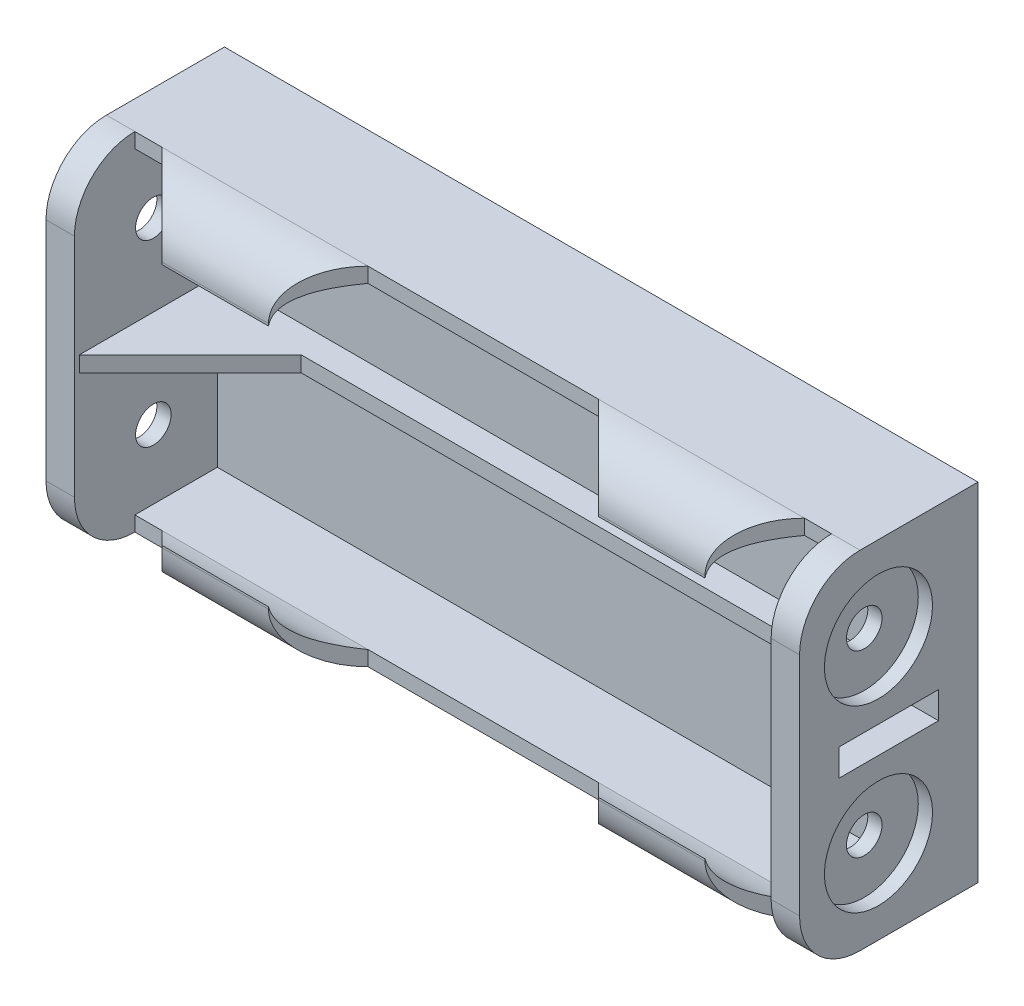
SolidWorks part; units mm, degrees
ref_plane "Přední rovina" through (0, 0, 0) normal (0, 0, 1) x (1, 0, 0)
ref_plane "Horní rovina" through (0, 0, 0) normal (0, 1, 0) x (1, 0, 0)
ref_plane "Pravá rovina" through (0, 0, 0) normal (1, 0, 0) x (0, 0, -1)
sketch "Skica1" plane through (0, 0, 0) normal (0, 0, 1) x (1, 0, 0)
  line L1 (-26.5, -12.2) -> (26.5, -12.2)
  line L2 (-26.5, -12.2) -> (-26.5, 12.2)
  line L3 (-26.5, 12.2) -> (26.5, 12.2)
  line L4 (26.5, -12.2) -> (26.5, 12.2)
  line L5 (-26.5, -12.2) -> (26.5, 12.2) construction
  line L6 (-26.5, 12.2) -> (26.5, -12.2) construction
  point P0 (0, 0)
  dimension "D1" = 53
  dimension "D2" = 24.4
extrude "Přidat vysunutím1" add sketch "Skica1" along normal blind 2.5
sketch "Skica2" plane through (0, 0, 2.5) normal (0, 0, 1) x (1, 0, 0)
  line L0 (26.5, 12.2) -> (-26.5, 12.2) construction
  line L1 (-24.5, 11.15) -> (24.5, 11.15)
  line L2 (-24.5, 11.15) -> (-24.5, 12.2)
  line L3 (-24.5, 12.2) -> (24.5, 12.2)
  line L4 (24.5, 11.15) -> (24.5, 12.2)
  line L5 (-26.5, 12.2) -> (-26.5, -12.2) construction
  line L6 (26.5, -12.2) -> (26.5, 12.2) construction
  line L7 (-26.5, -12.2) -> (26.5, -12.2) construction
  line L8 (-24.5, -12.2) -> (24.5, -12.2)
  line L9 (-24.5, -12.2) -> (-24.5, -11.15)
  line L10 (-24.5, -11.15) -> (24.5, -11.15)
  line L11 (24.5, -12.2) -> (24.5, -11.15)
  dimension "D1" = 2
  dimension "D2" = 2
  dimension "D3" = 2
  dimension "D4" = 2
  dimension "D5" = 1.05
  dimension "D6" = 1.05
extrude "Přidat vysunutím2" add sketch "Skica2" along normal blind 9.3
sketch "Skica3" plane through (0, 0, 11.8) normal (0, 0, 1) x (1, 0, 0)
  line L0 (-24.5, -12.2) -> (24.5, -12.2) construction
  line L1 (-8.1, -12.2) -> (8.1, -12.2)
  line L2 (-8.1, -12.2) -> (-8.1, -11.15)
  line L3 (-8.1, -11.15) -> (8.1, -11.15)
  line L4 (8.1, -12.2) -> (8.1, -11.15)
  line L5 (24.5, -11.15) -> (-24.5, -11.15) construction
  line L6 (24.5, 12.2) -> (-24.5, 12.2) construction
  line L7 (8.1, 12.2) -> (-8.1, 12.2)
  line L8 (8.1, 12.2) -> (8.1, 11.15)
  line L9 (8.1, 11.15) -> (-8.1, 11.15)
  line L10 (-8.1, 12.2) -> (-8.1, 11.15)
  line L11 (-24.5, 11.15) -> (24.5, 11.15) construction
  line L12 (0, 12.25) -> (0, -12.2) construction
  line L14 (-24.5, 11.15) -> (-22.6, 11.15)
  line L15 (-24.5, 11.15) -> (-24.5, 12.2)
  line L16 (-24.5, 12.2) -> (-22.6, 12.2)
  line L17 (-22.6, 11.15) -> (-22.6, 12.2)
  line L18 (-24.5, -12.2) -> (-22.6, -12.2)
  line L19 (-24.5, -12.2) -> (-24.5, -11.15)
  line L20 (-24.5, -11.15) -> (-22.6, -11.15)
  line L21 (-22.6, -12.2) -> (-22.6, -11.15)
  line L22 (24.5, 11.15) -> (22.6, 11.15)
  line L23 (24.5, 11.15) -> (24.5, 12.2)
  line L24 (24.5, 12.2) -> (22.6, 12.2)
  line L25 (22.6, 11.15) -> (22.6, 12.2)
  line L26 (24.5, -12.2) -> (22.6, -12.2)
  line L27 (24.5, -12.2) -> (24.5, -11.15)
  line L28 (24.5, -11.15) -> (22.6, -11.15)
  line L29 (22.6, -12.2) -> (22.6, -11.15)
  dimension "D1" = 16.2
  dimension "D2" = 1.9
  dimension "D3" = 1.9
extrude "Odebrat vysunutím1" cut sketch "Skica3" against normal blind 3.5
sketch "Skica6" plane through (0, -11.15, 0) normal (0, 1, 0) x (1, 0, 0)
  line L1 (22.6, -8.3) -> (8.1, -8.3)
  line L2 (22.6, -8.3) -> (22.6, -11.8)
  line L3 (22.6, -11.8) -> (8.1, -11.8)
  line L4 (8.1, -8.3) -> (8.1, -11.8)
  line L5 (-8.1, -8.3) -> (-22.6, -8.3)
  line L6 (-8.1, -8.3) -> (-8.1, -11.8)
  line L7 (-8.1, -11.8) -> (-22.6, -11.8)
  line L8 (-22.6, -8.3) -> (-22.6, -11.8)
sketch "Skica7" plane through (0, 11.15, 0) normal (0, -1, 0) x (-1, 0, 0)
  line L1 (22.6, -8.3) -> (8.1, -8.3)
  line L2 (22.6, -8.3) -> (22.6, -11.8)
  line L3 (22.6, -11.8) -> (8.1, -11.8)
  line L4 (8.1, -8.3) -> (8.1, -11.8)
  line L5 (-8.1, -8.3) -> (-22.6, -8.3)
  line L6 (-8.1, -8.3) -> (-8.1, -11.8)
  line L7 (-8.1, -11.8) -> (-22.6, -11.8)
  line L8 (-22.6, -8.3) -> (-22.6, -11.8)
extrude "Přidat vysunutím3" add sketch "Skica7" along normal blind 2.6
extrude "Přidat vysunutím4" add sketch "Skica6" along normal blind 2.6 contours L7 L8 L5 L6
sketch "Skica8" plane through (0, -11.15, 0) normal (0, 1, 0) x (1, 0, 0)
  line L1 (22.6, -8.3) -> (8.1, -8.3)
  line L2 (22.6, -8.3) -> (22.6, -11.8)
  line L3 (22.6, -11.8) -> (8.1, -11.8)
  line L4 (8.1, -8.3) -> (8.1, -11.8)
extrude "Přidat vysunutím5" add sketch "Skica8" along normal blind 2.6
fillet "Zaoblit3" radius 3.5 4 edges at (15.35, 12.2, 11.8) (-15.35, 12.2, 11.8) (-15.35, -12.2, 11.8) (15.35, -12.2, 11.8)
sketch "Skica11" plane through (22.6, 0, 0) normal (1, 0, 0) x (0, 0, -1)
  line L0 (-11.8, -8.55) -> (-8.3, -8.55)
  line L1 (-8.3, -8.55) -> (-8.3, -11.15)
  spline S0 degree 2 poles (-8.3, -11.15) (-11.4896, -10.5739) (-11.8, -8.55) knots 0 0 0 0.822636 0.822636 0.822636
extrude "Odebrat vysunutím2" cut sketch "Skica11" against normal up to vertex
sketch "Skica13" plane through (22.6, 0, 0) normal (1, 0, 0) x (0, 0, -1)
  line L0 (-11.8, 8.55) -> (-8.3, 8.55)
  line L1 (-8.3, 8.55) -> (-8.3, 11.15)
  spline S0 degree 2 poles (-8.3, 11.15) (-11.5945, 10.6267) (-11.8, 8.55) knots 0 0 0 0.882557 0.882557 0.882557
extrude "Odebrat vysunutím3" cut sketch "Skica13" against normal up to vertex
chamfer "Zkosení3" distance 3.5 angle 45 8 edges at (-22.6, -8.625, 11.8) (-22.6, 8.625, 11.8) (22.6, 8.625, 11.8) (22.6, -8.625, 11.8)
sketch "Skica14" plane through (0, 0, 2.5) normal (0, 0, 1) x (1, 0, 0)
  line L1 (26.5, -12.2) -> (24.5, -12.2)
  line L2 (26.5, -12.2) -> (26.5, 12.2)
  line L3 (26.5, 12.2) -> (24.5, 12.2)
  line L4 (24.5, -12.2) -> (24.5, 12.2)
  line L5 (-26.5, -12.2) -> (-24.5, -12.2)
  line L6 (-26.5, -12.2) -> (-26.5, 12.2)
  line L7 (-26.5, 12.2) -> (-24.5, 12.2)
  line L8 (-24.5, -12.2) -> (-24.5, 12.2)
extrude "Přidat vysunutím6" add sketch "Skica14" along normal blind 10.05
fillet "Zaoblit4" radius 4.25 4 edges at (-25.5, 12.2, 12.55) (-25.5, -12.2, 12.55) (25.5, -12.2, 12.55) (25.5, 12.2, 12.55)
sketch "Skica17" plane through (26.5, 0, 0) normal (1, 0, 0) x (0, 0, -1)
  line L0 (-12.55, 0) -> (0, 0) construction
  line L1 (-12.55, -7.95) -> (-12.55, 7.95) construction
  line L2 (0, -12.2) -> (0, 12.2) construction
  line L4 (-2.775, -0.95) -> (-9.775, -0.95)
  line L5 (-2.775, -0.95) -> (-2.775, 0.95)
  line L6 (-2.775, 0.95) -> (-9.775, 0.95)
  line L7 (-9.775, -0.95) -> (-9.775, 0.95)
  line L8 (-2.775, -0.95) -> (-9.775, 0.95) construction
  line L9 (-2.775, 0.95) -> (-9.775, -0.95) construction
  point P6 (-6.275, 0)
  dimension "D1" = 1.9
  dimension "D2" = 7
extrude "Odebrat vysunutím4" cut sketch "Skica17" against normal blind 2.05
sketch "Skica18" plane through (26.5, 0, 0) normal (1, 0, 0) x (0, 0, -1)
  line L0 (-7, -6.3) -> (-7, 6.3) construction
  line L1 (-7, 6.3) -> (-12.55, 0) construction
  line L2 (-12.55, -7.95) -> (-12.55, 7.95) construction
  line L3 (-12.55, 0) -> (0, 0) construction
  line L4 (0, -12.2) -> (0, 12.2) construction
  line L5 (-8.3, -12.2) -> (0, -12.2) construction
  line L6 (-8.3, 12.2) -> (0, 12.2) construction
  circle A0 centre (-7, 6.3) radius 3.8
  circle A1 centre (-7, -6.3) radius 3.8
  dimension "D1" = 7.6
  dimension "D3" = 2.1
  dimension "D4" = 1.75
  dimension "D2" = 2.1
sketch "Skica19" plane through (0, 0, 2.5) normal (0, 0, 1) x (1, 0, 0)
  line L0 (0, 11.15) -> (0, -11.15) construction
  line L1 (-24.5, 11.15) -> (24.5, 11.15) construction
  line L2 (24.5, -11.15) -> (-24.5, -11.15) construction
extrude "Odebrat vysunutím5" cut sketch "Skica18" against normal blind 1
sketch "Skica20" plane through (25.5, 0, 0) normal (1, 0, 0) x (0, 0, -1)
  circle A0 centre (-7, -6.3) radius 1.25
  circle A1 centre (-7, 6.3) radius 1.25
  dimension "D1" = 2.5
extrude "Odebrat vysunutím6" cut sketch "Skica20" against normal blind 1
sketch "Skica21" plane through (-26.5, 0, 0) normal (-1, 0, 0) x (0, 0, 1)
  line L0 (0, 0) -> (12.55, 0) construction
  line L1 (0, 12.2) -> (0, -12.2) construction
  line L2 (12.55, 7.95) -> (12.55, -7.95) construction
  line L3 (7, 6.3) -> (7, -6.3) construction
  line L4 (8.3, 12.2) -> (0, 12.2) construction
  line L8 (8.3, -12.2) -> (0, -12.2) construction
  circle A0 centre (7, 6.3) radius 3.8
  circle A1 centre (7, -6.3) radius 3.8
  dimension "D2" = 2.1
  dimension "D3" = 1.75
  dimension "D4" = 7.6
  dimension "D1" = 2.1
extrude "Odebrat vysunutím7" cut sketch "Skica21" against normal blind 1
sketch "Skica22" plane through (-25.5, 0, 0) normal (-1, 0, 0) x (0, 0, 1)
  circle A0 centre (7, -6.3) radius 1.25
  circle A1 centre (7, 6.3) radius 1.25
  dimension "D1" = 2.5
extrude "Odebrat vysunutím8" cut sketch "Skica22" against normal blind 1
sketch "Skica23" plane through (0, 0, 2.5) normal (0, 0, 1) x (1, 0, 0)
  line L0 (-24.5, -11.15) -> (-24.5, 11.15) construction
  line L1 (24.5, -0.55) -> (-24.5, -0.55)
  line L2 (24.5, -0.55) -> (24.5, 0.55)
  line L3 (24.5, 0.55) -> (-24.5, 0.55)
  line L4 (-24.5, -0.55) -> (-24.5, 0.55)
  line L5 (24.5, -0.55) -> (-24.5, 0.55) construction
  line L6 (24.5, 0.55) -> (-24.5, -0.55) construction
  point P0 (0, 0)
  dimension "D1" = 1.1
extrude "Přidat vysunutím7" add sketch "Skica23" along normal blind 9.7
sketch "Skica24" plane through (0, 0, 12.2) normal (0, 0, 1) x (1, 0, 0)
  line L0 (0, -0.55) -> (0, 0.55) construction
  line L1 (-24.5, -0.55) -> (24.5, -0.55) construction
  line L2 (24.5, 0.55) -> (-24.5, 0.55) construction
  line L4 (13, -0.55) -> (-13, -0.55)
  line L5 (13, -0.55) -> (13, 0.55)
  line L6 (13, 0.55) -> (-13, 0.55)
  line L7 (-13, -0.55) -> (-13, 0.55)
  line L8 (13, -0.55) -> (-13, 0.55) construction
  line L9 (13, 0.55) -> (-13, -0.55) construction
  point P6 (0, 0)
  dimension "D1" = 26
extrude "Odebrat vysunutím9" cut sketch "Skica24" against normal blind 7.8
chamfer "Zkosení5" distance 11.5 angle 45 1 edges at (-13, 0, 12.2)
chamfer "Zkosení6" distance 11.5 angle 45 1 edges at (13, 0, 12.2)
